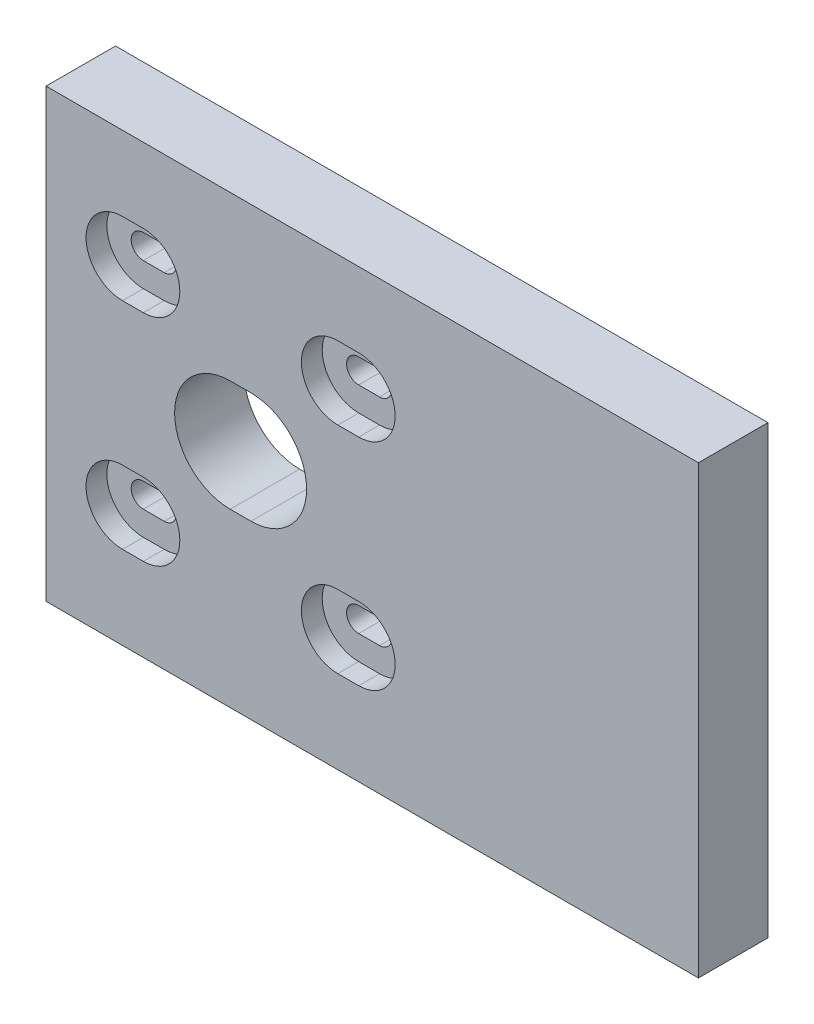
SolidWorks part; units mm, degrees
ref_plane "Front Plane" through (0, 0, 0) normal (0, 0, 1) x (1, 0, 0)
ref_plane "Top Plane" through (0, 0, 0) normal (0, 1, 0) x (1, 0, 0)
ref_plane "Right Plane" through (0, 0, 0) normal (1, 0, 0) x (0, 0, -1)
sketch "Sketch1" plane through (0, 0, 0) normal (0, 0, 1) x (1, 0, 0)
  line L1 (-50.949, 32.0052) -> (42.9629, 32.0052)
  line L2 (-50.949, 32.0052) -> (-50.949, -32.232)
  line L3 (-50.949, -32.232) -> (42.9629, -32.232)
  line L4 (42.9629, 32.0052) -> (42.9629, -32.232)
extrude "Boss-Extrude1" add sketch "Sketch1" along normal blind 10
sketch "Sketch2" plane through (0, 0, 10) normal (0, 0, 1) x (1, 0, 0)
  line L0 (-45.949, 22.0052) -> (-2.949, -20.9948) construction
  line L1 (-45.949, 22.0052) -> (-2.949, 22.0052) construction
  line L2 (-45.949, 22.0052) -> (-45.949, -20.9948) construction
  line L3 (-45.949, -20.9948) -> (-2.949, -20.9948) construction
  line L4 (-2.949, 22.0052) -> (-2.949, -20.9948) construction
  line L5 (-2.949, 22.0052) -> (-45.949, -20.9948) construction
  line L6 (-39.949, 16.0052) -> (-36.949, 16.0052) construction
  line L7 (-39.949, 17.7552) -> (-36.949, 17.7552)
  line L8 (-39.949, 14.2552) -> (-36.949, 14.2552)
  line L9 (-8.949, 16.0052) -> (-5.949, 16.0052) construction
  line L10 (-8.949, 17.7552) -> (-5.949, 17.7552)
  line L11 (-8.949, 14.2552) -> (-5.949, 14.2552)
  line L12 (-8.949, -14.9948) -> (-5.949, -14.9948) construction
  line L13 (-8.949, -13.2448) -> (-5.949, -13.2448)
  line L14 (-8.949, -16.7448) -> (-5.949, -16.7448)
  line L15 (-39.949, -14.9948) -> (-36.949, -14.9948) construction
  line L16 (-39.949, -13.2448) -> (-36.949, -13.2448)
  line L17 (-39.949, -16.7448) -> (-36.949, -16.7448)
  line L18 (-24.449, 0.5052) -> (-21.449, 0.5052) construction
  line L19 (-24.449, 8.5052) -> (-21.449, 8.5052)
  line L20 (-24.449, -7.4948) -> (-21.449, -7.4948)
  line L21 (42.9629, 32.0052) -> (-50.949, 32.0052) construction
  line L22 (-50.949, 32.0052) -> (-50.949, -32.232) construction
  arc A0 (-39.949, 17.7552) -> (-39.949, 14.2552) centre (-39.949, 16.0052) ccw
  arc A1 (-36.949, 14.2552) -> (-36.949, 17.7552) centre (-36.949, 16.0052) ccw
  arc A2 (-8.949, 17.7552) -> (-8.949, 14.2552) centre (-8.949, 16.0052) ccw
  arc A3 (-5.949, 14.2552) -> (-5.949, 17.7552) centre (-5.949, 16.0052) ccw
  arc A4 (-8.949, -13.2448) -> (-8.949, -16.7448) centre (-8.949, -14.9948) ccw
  arc A5 (-5.949, -16.7448) -> (-5.949, -13.2448) centre (-5.949, -14.9948) ccw
  arc A6 (-39.949, -13.2448) -> (-39.949, -16.7448) centre (-39.949, -14.9948) ccw
  arc A7 (-36.949, -16.7448) -> (-36.949, -13.2448) centre (-36.949, -14.9948) ccw
  arc A8 (-24.449, 8.5052) -> (-24.449, -7.4948) centre (-24.449, 0.5052) ccw
  arc A9 (-21.449, -7.4948) -> (-21.449, 8.5052) centre (-21.449, 0.5052) ccw
  point P6 (-38.449, 16.0052)
  point P11 (-7.449, 16.0052)
  point P18 (-7.449, -14.9948)
  point P25 (-38.449, -14.9948)
  point P34 (-22.949, 0.5052)
  dimension "D2" = 1.75
  dimension "D4" = 8
  dimension "D1" = 3
  dimension "D3" = 3
  dimension "D5" = 31
  dimension "D6" = 43
  dimension "D7" = 10
  dimension "D8" = 5
extrude "Cut-Extrude1" cut sketch "Sketch2" against normal blind 20
sketch "Sketch3" plane through (0, 0, 10) normal (0, 0, 1) x (1, 0, 0)
  line L0 (-36.949, 17.7552) -> (-39.949, 17.7552) construction
  line L1 (-39.949, 14.2552) -> (-36.949, 14.2552) construction
  line L2 (-5.949, 17.7552) -> (-8.949, 17.7552) construction
  line L3 (-8.949, 14.2552) -> (-5.949, 14.2552) construction
  line L4 (-5.949, -13.2448) -> (-8.949, -13.2448) construction
  line L5 (-8.949, -16.7448) -> (-5.949, -16.7448) construction
  line L6 (-39.949, -16.7448) -> (-36.949, -16.7448) construction
  line L7 (-36.949, -13.2448) -> (-39.949, -13.2448) construction
  line L8 (-36.949, 17.7552) -> (-39.949, 17.7552) construction
  line L9 (-39.949, 14.2552) -> (-36.949, 14.2552) construction
  line L10 (-5.949, 17.7552) -> (-8.949, 17.7552) construction
  line L11 (-8.949, 14.2552) -> (-5.949, 14.2552) construction
  line L12 (-5.949, -13.2448) -> (-8.949, -13.2448) construction
  line L13 (-8.949, -16.7448) -> (-5.949, -16.7448) construction
  line L14 (-39.949, -16.7448) -> (-36.949, -16.7448) construction
  line L15 (-36.949, -13.2448) -> (-39.949, -13.2448) construction
  line L16 (-36.949, 21.2552) -> (-39.949, 21.2552)
  line L17 (-39.949, 10.7552) -> (-36.949, 10.7552)
  line L18 (-5.949, 21.2552) -> (-8.949, 21.2552)
  line L19 (-8.949, 10.7552) -> (-5.949, 10.7552)
  line L20 (-5.949, -9.7448) -> (-8.949, -9.7448)
  line L21 (-8.949, -20.2448) -> (-5.949, -20.2448)
  line L22 (-39.949, -20.2448) -> (-36.949, -20.2448)
  line L23 (-36.949, -9.7448) -> (-39.949, -9.7448)
  arc A0 (-39.949, 17.7552) -> (-39.949, 14.2552) centre (-39.949, 16.0052) ccw construction
  arc A1 (-36.949, 14.2552) -> (-36.949, 17.7552) centre (-36.949, 16.0052) ccw construction
  arc A2 (-8.949, 17.7552) -> (-8.949, 14.2552) centre (-8.949, 16.0052) ccw construction
  arc A3 (-5.949, 14.2552) -> (-5.949, 17.7552) centre (-5.949, 16.0052) ccw construction
  arc A4 (-5.949, -16.7448) -> (-5.949, -13.2448) centre (-5.949, -14.9948) ccw construction
  arc A5 (-8.949, -13.2448) -> (-8.949, -16.7448) centre (-8.949, -14.9948) ccw construction
  arc A6 (-36.949, -16.7448) -> (-36.949, -13.2448) centre (-36.949, -14.9948) ccw construction
  arc A7 (-39.949, -13.2448) -> (-39.949, -16.7448) centre (-39.949, -14.9948) ccw construction
  arc A8 (-39.949, 17.7552) -> (-39.949, 14.2552) centre (-39.949, 16.0052) ccw construction
  arc A9 (-36.949, 14.2552) -> (-36.949, 17.7552) centre (-36.949, 16.0052) ccw construction
  arc A10 (-8.949, 17.7552) -> (-8.949, 14.2552) centre (-8.949, 16.0052) ccw construction
  arc A11 (-5.949, 14.2552) -> (-5.949, 17.7552) centre (-5.949, 16.0052) ccw construction
  arc A12 (-5.949, -16.7448) -> (-5.949, -13.2448) centre (-5.949, -14.9948) ccw construction
  arc A13 (-8.949, -13.2448) -> (-8.949, -16.7448) centre (-8.949, -14.9948) ccw construction
  arc A14 (-36.949, -16.7448) -> (-36.949, -13.2448) centre (-36.949, -14.9948) ccw construction
  arc A15 (-39.949, -13.2448) -> (-39.949, -16.7448) centre (-39.949, -14.9948) ccw construction
  arc A16 (-39.949, 21.2552) -> (-39.949, 10.7552) centre (-39.949, 16.0052) ccw
  arc A17 (-36.949, 10.7552) -> (-36.949, 21.2552) centre (-36.949, 16.0052) ccw
  arc A18 (-8.949, 21.2552) -> (-8.949, 10.7552) centre (-8.949, 16.0052) ccw
  arc A19 (-5.949, 10.7552) -> (-5.949, 21.2552) centre (-5.949, 16.0052) ccw
  arc A20 (-8.949, -9.7448) -> (-8.949, -20.2448) centre (-8.949, -14.9948) ccw
  arc A21 (-5.949, -20.2448) -> (-5.949, -9.7448) centre (-5.949, -14.9948) ccw
  arc A22 (-36.949, -20.2448) -> (-36.949, -9.7448) centre (-36.949, -14.9948) ccw
  arc A23 (-39.949, -9.7448) -> (-39.949, -20.2448) centre (-39.949, -14.9948) ccw
  dimension "D1" = 3.5
extrude "Cut-Extrude2" cut sketch "Sketch3" against normal blind 3
